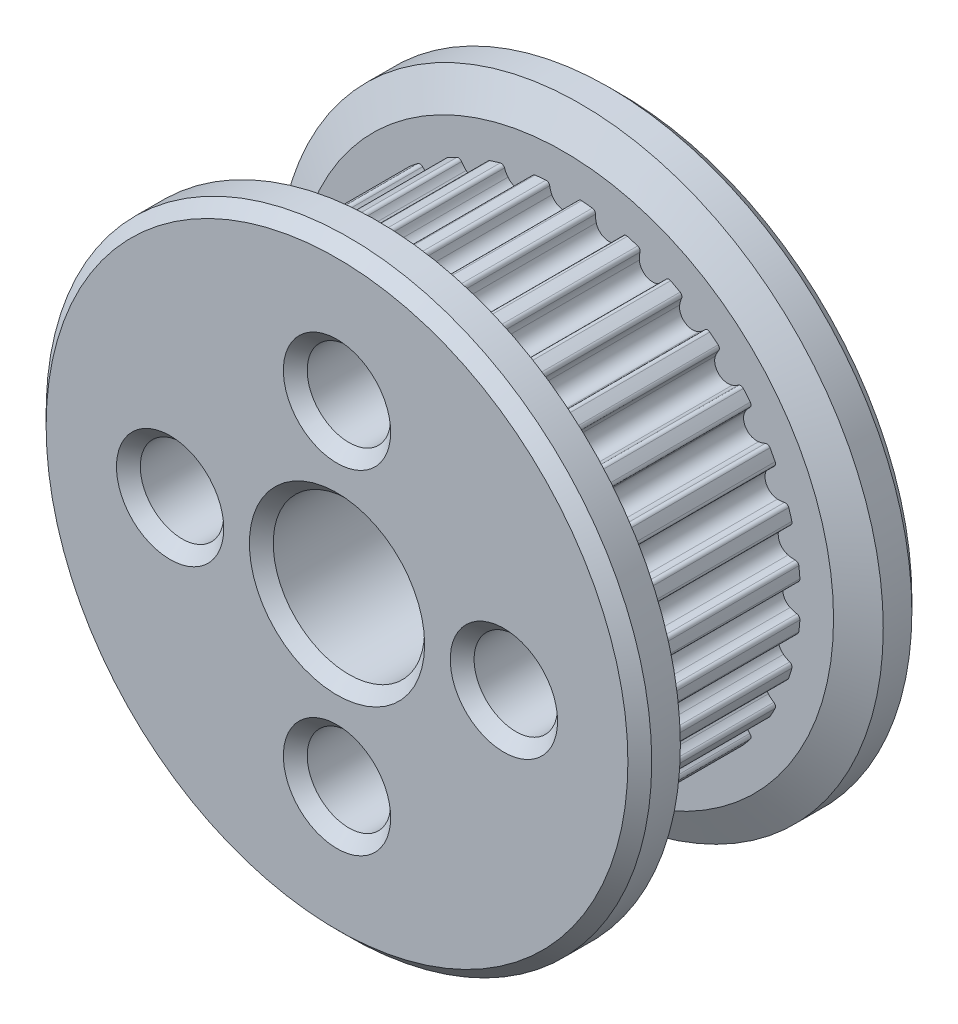
SolidWorks part; units mm, degrees
note: '?' marks a value the reader was unsure of.
ref_plane "Front Plane" through (0, 0, 0) normal (0, 0, 1) x (1, 0, 0)
ref_plane "Top Plane" through (0, 0, 0) normal (0, 1, 0) x (1, 0, 0)
ref_plane "Right Plane" through (0, 0, 0) normal (1, 0, 0) x (0, 0, -1)
sketch "Sketch1" plane through (0, 0, 0) normal (0, 0, 1) x (1, 0, 0)
  line L1 (-1.8294, 9.1815) -> (1.8294, 9.1815) construction
  line L4 (0, 0) -> (0, 9.1815) construction
  line L5 (0, 9.1815) -> (0, 13.7598) construction
  line L6 (0, 10.1855) -> (1.9903, 9.9891) construction
  line L7 (1.9903, 9.9891) -> (2.798, 9.8282) construction
  line L8 (1.9903, 9.9891) -> (1.8294, 9.1815) construction
  line L9 (-1.9903, 9.9891) -> (-1.8294, 9.1815) construction
  line L10 (-1.9407, 9.74) -> (-2.5305, 12.7)
  line L11 (-2.5305, 12.7) -> (2.5305, 12.7)
  line L12 (2.5305, 12.7) -> (1.9407, 9.74)
  circle A0 centre (0, 0) radius 10.1855 construction
  circle A1 centre (0, 0) radius 12.7 construction
  circle A2 centre (0, 0) radius 9.9315 construction
  arc A3 (-0.4989, 9.4933) -> (0.4989, 9.4933) centre (0, 9.7365) ccw
  arc A4 (-0.4989, 9.4933) -> (-0.588, 9.7769) centre (0.4, 9.9315) cw
  arc A5 (-1.9407, 9.74) -> (-0.7475, 9.9033) centre (0, 0) cw
  arc A6 (-0.588, 9.7769) -> (-0.7475, 9.9033) centre (-0.7362, 9.7538) ccw
  arc A7 (1.9407, 9.74) -> (0.7475, 9.9033) centre (0, 0) ccw
  arc A8 (0.588, 9.7769) -> (0.7475, 9.9033) centre (0.7362, 9.7538) cw
  arc A9 (0.4989, 9.4933) -> (0.588, 9.7769) centre (-0.4, 9.9315) ccw
  point P6 (0, 20.9083)
  point P11 (0, 10.1855)
  point P13 (0, 12.7)
  point P14 (0, 9.9315)
  dimension "D1" = 7.1486
  dimension "D2" = 3.5743
sketch "Sketch2" plane through (0, 0, 0) normal (1, 0, 0) x (0, 0, -1)
  line L0 (-8.7249, 3.175) -> (8.7249, 3.175)
  line L1 (-8.7249, 3.175) -> (-8.7249, 7.595)
  line L2 (-8.7249, 7.595) -> (-1.1851, 7.595)
  line L3 (-1.1851, 7.595) -> (-1.1851, 12.7)
  line L4 (-1.1851, 12.7) -> (0.2149, 12.7) construction
  line L5 (0.2149, 12.7) -> (0.2149, 9.9315) construction
  line L6 (0.2149, 9.9315) -> (7.3249, 9.9315)
  line L7 (7.3249, 9.9315) -> (7.3249, 12.7) construction
  line L8 (7.3249, 12.7) -> (8.7249, 12.7) construction
  line L9 (8.7249, 12.7) -> (8.7249, 3.175)
  line L10 (-8.7249, 0) -> (8.7249, 0) construction
  line L11 (8.0249, 12.7) -> (7.3249, 11.3157)
  line L12 (0.2149, 11.3157) -> (-0.4851, 12.7)
  line L13 (-1.1851, 12.7) -> (-0.4851, 12.7)
  line L14 (0.2149, 11.3157) -> (0.2149, 9.9315)
  line L15 (7.3249, 9.9315) -> (7.3249, 11.3157)
  line L16 (8.0249, 12.7) -> (8.7249, 12.7)
  arc A0 (0.2149, 11.3157) -> (-0.4851, 12.7) centre (-1.5038, 11.3157) ccw construction
  arc A1 (7.3249, 11.3157) -> (8.0249, 12.7) centre (9.0436, 11.3157) cw construction
  point P12 (0.2149, 11.3157)
  point P14 (-0.4851, 12.7)
  point P20 (7.3249, 11.3157)
  point P21 (8.0249, 12.7)
  point P25 (7.3249, 0)
  point P26 (0.2149, 0)
revolve "Revolve1" add sketch "Sketch2" angle 360 mid plane about L10
sketch "Sketch3" plane through (0, 0, 0) normal (0, 0, 1) x (1, 0, 0)
  line L6 (2.5305, 12.7) -> (-2.5305, 12.7)
  line L7 (1.9407, 9.74) -> (2.5305, 12.7)
  line L8 (-2.5305, 12.7) -> (-1.9407, 9.74)
  line L9 (2.5305, 12.7) -> (-2.5305, 12.7)
  line L10 (1.9407, 9.74) -> (2.5305, 12.7)
  line L11 (-2.5305, 12.7) -> (-1.9407, 9.74)
  arc A8 (1.9407, 9.74) -> (0.7475, 9.9033) centre (0, 0) ccw
  arc A9 (0.7475, 9.9033) -> (0.588, 9.7769) centre (0.7362, 9.7538) ccw
  arc A10 (0.4989, 9.4933) -> (0.588, 9.7769) centre (-0.4, 9.9315) ccw
  arc A11 (-0.4989, 9.4933) -> (0.4989, 9.4933) centre (0, 9.7365) ccw
  arc A12 (-0.588, 9.7769) -> (-0.4989, 9.4933) centre (0.4, 9.9315) ccw
  arc A13 (-0.588, 9.7769) -> (-0.7475, 9.9033) centre (-0.7362, 9.7538) ccw
  arc A14 (-0.7475, 9.9033) -> (-1.9407, 9.74) centre (0, 0) ccw
  arc A15 (1.9407, 9.74) -> (0.7475, 9.9033) centre (0, 0) ccw
  arc A16 (0.7475, 9.9033) -> (0.588, 9.7769) centre (0.7362, 9.7538) ccw
  arc A17 (0.4989, 9.4933) -> (0.588, 9.7769) centre (-0.4, 9.9315) ccw
  arc A18 (-0.4989, 9.4933) -> (0.4989, 9.4933) centre (0, 9.7365) ccw
  arc A19 (-0.588, 9.7769) -> (-0.4989, 9.4933) centre (0.4, 9.9315) ccw
  arc A20 (-0.588, 9.7769) -> (-0.7475, 9.9033) centre (-0.7362, 9.7538) ccw
  arc A21 (-0.7475, 9.9033) -> (-1.9407, 9.74) centre (0, 0) ccw
  dimension "D1" = 0
extrude "Cut-Extrude1" cut sketch "Sketch3" against normal up to vertex (7.3249 mm away) from vertex at -0.2149 starting at point (0, 9.9315, -0.2149)
pattern_circular "CirPattern1" count 32 over 360 about axis through (0, 0, 0) along (0, 0, 1) of "Cut-Extrude1"
sketch "Sketch4" plane through (0, 0, 0) normal (1, 0, 0) x (0, -1, 0)
  line L0 (0, -1.1851) -> (0, -8.7249) construction
  line L1 (-7.595, -1.1851) -> (7.595, -1.1851) construction
  line L2 (-7.595, -8.7249) -> (7.595, -8.7249) construction
  circle A0 centre (0, -4.955) radius 1.7526
extrude "Cut-Extrude2" cut sketch "Sketch4" along normal through all
ref_plane "Plane1" through (0, 0, 4.955) normal (0, 0, 1) x (1, 0, 0)
sketch "Sketch5" plane through (0, 0, 4.955) normal (0, 0, 1) x (1, 0, 0)
  line L0 (0, 0.1664) -> (0, 7.595) construction
  line L1 (3.175, -1.3716) -> (3.175, 0)
  line L2 (3.556, -1.7526) -> (7.009, -1.7526)
  line L3 (3.175, 0) -> (7.595, 0) construction
  line L4 (3.175, 0) -> (7.39, 0)
  line L5 (7.39, 0) -> (7.39, -1.3716)
  line L6 (3.556, -1.7526) -> (3.175, -1.3716)
  line L7 (7.39, -1.3716) -> (7.009, -1.7526)
  circle A0 centre (0, 0) radius 7.595 construction
  circle A1 centre (0, 0) radius 3.175 construction
  point P2 (3.175, -1.7526)
  point P11 (7.39, -1.7526)
revolve "Revolve2" add sketch "Sketch5" angle 360 mid plane about L4
sketch "Sketch6" plane through (7.39, 5.3841, 0) normal (-1, 0, 0) x (0, -1, 0)
  line L1 (5.3841, 5.9669) -> (4.5078, 5.4609)
  line L2 (4.5078, 5.4609) -> (4.5078, 4.4491)
  line L3 (4.5078, 4.4491) -> (5.3841, 3.9431)
  line L4 (5.3841, 3.9431) -> (6.2604, 4.4491)
  line L5 (6.2604, 4.4491) -> (6.2604, 5.4609)
  line L6 (6.2604, 5.4609) -> (5.3841, 5.9669)
  circle A0 centre (5.3841, 4.955) radius 0.8763 construction
  dimension "D1" = 1.7526
extrude "Cut-Extrude3" cut sketch "Sketch6" along normal blind 1.3144
pattern_circular "CirPattern2" count 2 over 90 about axis through (0, 0, 0) along (0, 0, 1) of "Cut-Extrude2", "Revolve2", "Cut-Extrude3"
chamfer "Chamfer1" distance 0.3798 angle 45 2 edges at (3.175, 0, 8.7249) (7.595, 0, 8.7249)
ref_axis "Center Axis 1" through (0, 0, -8.7249) along (0, 0, 1)?
ref_plane "Contact Plane 1" through (0, 0, 8.7249) normal (0, 0, 1) x (1, 0, 0)
ref_plane "Contact Plane 2" through (0, 0, -8.7249) normal (0, 0, -1) x (-1, 0, 0)
sketch "Sketch7" plane through (0, 0, 1.1851) normal (0, 0, 1) x (1, 0, 0)
  circle A0 centre (0, 0) radius 7.595 construction
  circle A1 centre (0, 0) radius 7.595
extrude "Cut-Extrude4" cut sketch "Sketch7" along normal through all
sketch "Sketch8" plane through (0, 0, 1.1851) normal (0, 0, 1) x (1, 0, 0)
  circle A0 centre (0, 0) radius 7 construction
  circle A1 centre (0, 7) radius 1.75
  circle A2 centre (7, 0) radius 1.75
  circle A3 centre (0, -7) radius 1.75
  circle A4 centre (-7, 0) radius 1.75
  point P14 (0, 0)
  dimension "D2" = 14
  dimension "D3" = 3.5
  dimension "D1" = 4
extrude "Cut-Extrude5" cut sketch "Sketch8" against normal through all
ref_plane "Plane2" through (0, 0, -3.7699) normal (0, 0, 1) x (1, 0, 0)
sketch "Sketch9" plane through (0, 0, 1.1851) normal (0, 0, 1) x (1, 0, 0)
  circle A0 centre (0, 7) radius 1.75 construction
  circle A1 centre (0, 0) radius 12.7
  circle A2 centre (0, 0) radius 12.7
  circle A3 centre (0, -7) radius 1.75 construction
  circle A4 centre (7, 0) radius 1.75 construction
  circle A5 centre (0, 0) radius 3.175 construction
  circle A6 centre (-7, 0) radius 1.75 construction
  circle A7 centre (0, 7) radius 1.75
  circle A8 centre (0, -7) radius 1.75
  circle A9 centre (7, 0) radius 1.75
  circle A10 centre (0, 0) radius 3.175
  circle A11 centre (-7, 0) radius 1.75
  dimension "D1" = 0
extrude "Boss-Extrude1" add sketch "Sketch9" along normal blind 1
mirror "Mirror1" about plane through (0, 0, -3.7699) normal (0, 0, 1) of "Boss-Extrude1"
chamfer "Chamfer2" distance 0.5 angle 45 12 edges at (-5.25, 0, -9.7249) (3.175, 0, -9.7249) (8.75, 0, -9.7249) (1.75, -7, -9.7249) (1.75, 7, -9.7249) (12.7, 0, -9.7249) (-5.25, 0, 2.1851) (8.75, 0, 2.1851) (1.75, 7, 2.1851) (12.7, 0, 2.1851) (1.75, -7, 2.1851) (3.175, 0, 2.1851)
equation "\"D2@Sketch1\" = \"D1@Sketch1\"/2"
equation "\"D1@Sketch6\" = \"Set Screw@Sketch4\" / 2"
equation "\"D1@Cut-Extrude3\" = \"D1@Sketch6\"*.75"
equation "\"D1@Chamfer1\"=\"Hub Dia@Sketch2\"*.025"
